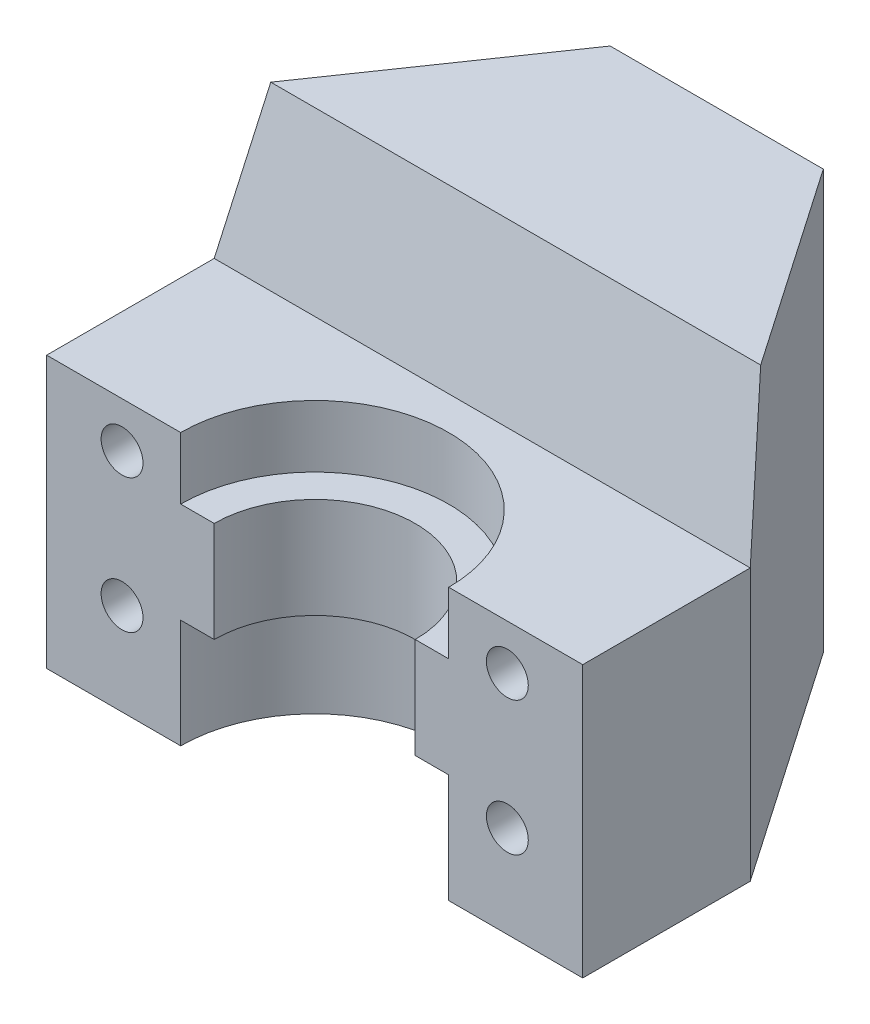
SolidWorks part; units mm, degrees
material "PLA"
ref_plane "Front Plane" through (0, 0, 0) normal (0, 0, 1) x (1, 0, 0)
ref_plane "Top Plane" through (0, 0, 0) normal (0, 1, 0) x (1, 0, 0)
ref_plane "Right Plane" through (0, 0, 0) normal (1, 0, 0) x (0, 0, -1)
sketch "Sketch1" plane through (0, 0, 0) normal (1, 0, 0) x (0, 0, -1)
  line L0 (0, 20) -> (12, 20) construction
  line L1 (0, 0) -> (12, 0)
  line L2 (0, 0) -> (0, 25)
  line L3 (0, 25) -> (12, 25)
  line L4 (12, 0) -> (12, 25)
  line L5 (0, 5) -> (12, 5) construction
  dimension "D1" = 15
  dimension "D2" = 12
  dimension "D3" = 25
  dimension "D4" = 5
extrude "Boss-Extrude1" add sketch "Sketch1" along normal mid plane 32 contours L4 L3 L2 L1
sketch "Sketch2" plane through (0, 0, 0) normal (0, 1, 0) x (1, 0, 0)
  line L0 (0, 0) -> (0, -2) construction
  line L1 (-16, -12) -> (16, -12)
  line L2 (-16, -12) -> (-16, -2)
  line L3 (-16, -2) -> (16, -2)
  line L4 (16, -12) -> (16, -2)
  line L5 (16, 0) -> (16, 12) construction
  dimension "D1" = 2
  dimension "D3" = 10
extrude "Boss-Extrude2" add sketch "Sketch2" along normal blind 16.2 separate body
sketch "Sketch3" plane through (16, 0, 0) normal (1, 0, 0) x (0, 0, -1)
  line L1 (-2, 0) -> (-2, 16.2) construction
  line L7 (0, 25) -> (0, 0) construction
  line L9 (-2, 0) -> (-2, 16.2)
  line L15 (0, 25) -> (0, 0)
  line L16 (0, 25) -> (-2, 16.2)
  line L17 (-2, 0) -> (0, 0)
extrude "Boss-Extrude3" add sketch "Sketch3" against normal up to surface (32 mm away) up to face at (-16, 8.1, 7)
hole_wizard "M5x0.8 Tapped Hole1" positions "Sketch7" profile "Sketch6" tap size "M5x0.8" standard "ANSI Metric"
sketch "Sketch7" plane through (0, 0, -12) normal (0, 0, -1) x (-1, 0, 0)
  line L0 (-16, 0) -> (16, 0) construction
  point P0 (0, 20)
  point P2 (0, 5)
  dimension "D1" = 15
  dimension "D2" = 5
sketch "Sketch6" plane through (0, 20, -12) normal (1, 0, 0) x (0, 1, 0)
  line L0 (0, 0) -> (0, 8.2618)
  line L1 (0, 8.2618) -> (2.1, 7)
  line L2 (2.1, 7) -> (2.1, 0)
  line L5 (2.1, 0) -> (0, 0)
  line L10 (0, 8.2618) -> (-2.1, 7) construction
  line L11 (0, -6.35) -> (0, 107.95) construction
  dimension "Tap Drill Dia." = 4.2
  dimension "Tap Drill Depth" = 7
  dimension "Drill Angle" = 118
cosmetic thread "Hole Thread1" parameters "D1"=4.2, "D2"=5
cosmetic thread "Hole Thread2" parameters "D1"=4.2, "D2"=5
sketch "Sketch9" plane through (0, 0, 0) normal (1, 0, 0) x (0, 0, -1)
  line L0 (-12, 16.2) -> (-4, 16.2)
  line L1 (-12, 16.2) -> (-12, 0) construction
  line L2 (-4, 16.2) -> (-4, 12.5)
  line L3 (-4, 12.5) -> (-6, 12.5)
  line L4 (-6, 12.5) -> (-6, 6.5)
  line L5 (-6, 6.5) -> (-4, 6.5)
  line L6 (-4, 6.5) -> (-4, 0)
  line L7 (-12, 0) -> (12, 0) construction
  line L8 (-4, 0) -> (-12, 0)
  line L9 (-12, 0) -> (-12, 16.2)
  line L10 (-12, 16.2) -> (-2, 16.2) construction
  dimension "D1" = 6
  dimension "D2" = 8
  dimension "D3" = 8
  dimension "D4" = 6.5
  dimension "D5" = 6
revolve "Cut-Revolve1" cut sketch "Sketch9" angle 360 about L9
sketch "Sketch10" plane through (0, 25, 0) normal (0, 1, 0) x (1, 0, 0)
  line L5 (16, -2) -> (16, 0) construction
  line L6 (-16, -2) -> (-6.3625, 12)
  line L7 (16, 12) -> (-16, 12) construction
  line L8 (-6.3625, 12) -> (-16, 12)
  line L9 (-16, 12) -> (-16, -2)
  line L10 (16, 12) -> (6.3625, 12)
  line L11 (16, -2) -> (16, 0)
  line L12 (6.3625, 12) -> (16, -2)
  line L13 (16, 12) -> (16, -2)
  line L14 (0, 0) -> (0, 12) construction
  line L15 (16, 0) -> (-16, 0) construction
  line M4 (-16, 12) -> (-16, 0)
  line M5 (-16, 0) -> (16, 0)
  line M6 (16, 0) -> (16, 12)
  line M7 (16, 12) -> (-16, 12)
  dimension "D1" = 12.725
extrude "Cut-Extrude2" cut sketch "Sketch10" against normal up to next contours L12 M7 M5 M6 | L12 L11 M5 | L6 M5 M7 M4 | L9 L6 M5 region at (-15.5411, 25, 0.6667) region at (-12.7301, 25, -7.5) region at (15.5411, 25, 0.6667) region at (12.7301, 25, -7.5)
hole_wizard "M3x0.5 Tapped Hole1" positions "Sketch12" profile "Sketch11" tap size "M3x0.5" standard "ANSI Metric"
sketch "Sketch12" plane through (0, 0, 12) normal (0, 0, 1) x (1, 0, 0)
  line L0 (0, 0) -> (0, 16.2) construction
  line L1 (8, 16.2) -> (-8, 16.2) construction
  line L4 (-11.5, 13.5) -> (-11.5, 5.5) construction
  line L7 (-11.5, 9.5) -> (0, 9.5) construction
  line L10 (-6, 6.5) -> (-6, 12.5) construction
  point P0 (-11.5, 13.5)
  point P2 (11.5, 13.5)
  point P7 (-11.5, 5.5)
  point P8 (11.5, 5.5)
  point P36 (-6, 9.5)
  dimension "D1" = 8
  dimension "D2" = 23
sketch "Sketch11" plane through (-11.5, 13.5, 12) normal (1, 0, 0) x (0, -1, 0)
  line L0 (0, 0) -> (0, 9.2511)
  line L1 (0, 9.2511) -> (1.25, 8.5)
  line L2 (1.25, 8.5) -> (1.25, 0)
  line L5 (1.25, 0) -> (0, 0)
  line L10 (0, 9.2511) -> (-1.25, 8.5) construction
  line L11 (0, -6.35) -> (0, 107.95) construction
  dimension "Tap Drill Dia." = 2.5
  dimension "Tap Drill Depth" = 8.5
  dimension "Drill Angle" = 118
cosmetic thread "Hole Thread3" parameters "D1"=6, "D2"=3
cosmetic thread "Hole Thread4" parameters "D1"=6, "D2"=3
cosmetic thread "Hole Thread5" parameters "D1"=6, "D2"=3
cosmetic thread "Hole Thread6" parameters "D1"=6, "D2"=3
